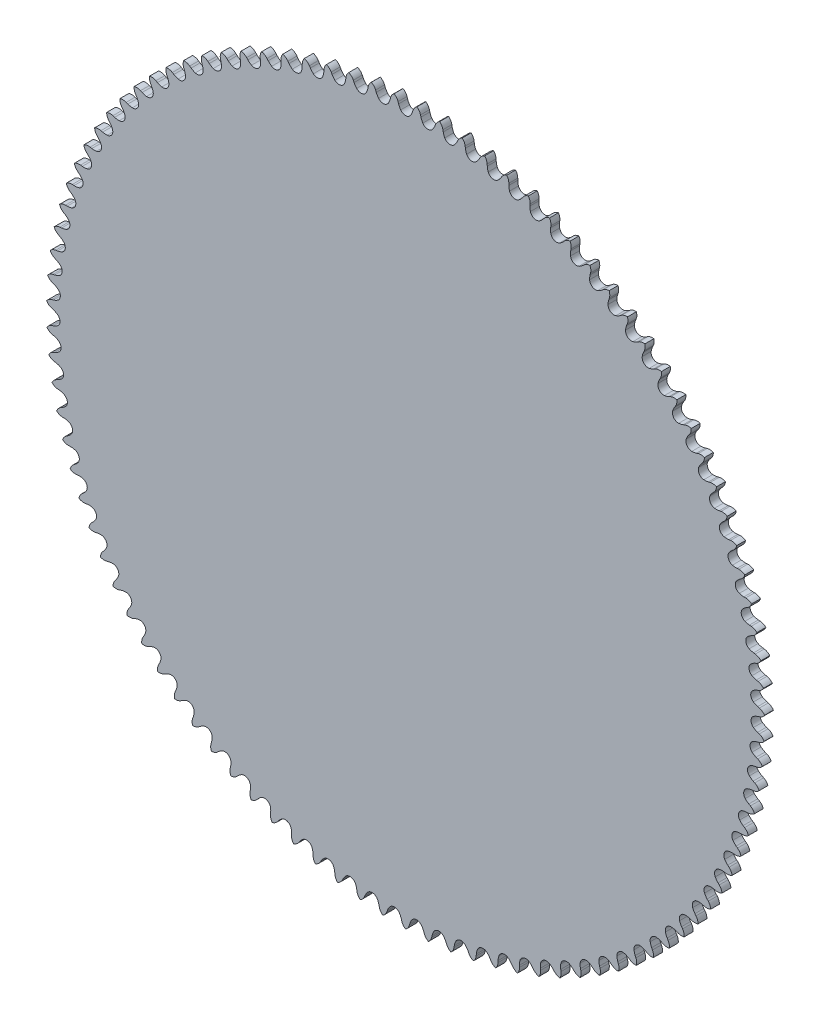
SolidWorks part; units mm, degrees
ref_plane "Front Plane" through (0, 0, 0) normal (0, 0, 1) x (1, 0, 0)
ref_plane "Top Plane" through (0, 0, 0) normal (0, 1, 0) x (1, 0, 0)
ref_plane "Right Plane" through (0, 0, 0) normal (1, 0, 0) x (0, 0, -1)
sketch "Sketch1" plane through (0, 0, 0) normal (0, 0, 1) x (1, 0, 0)
  line L0 (0, 0) -> (0, 31.4022) construction
  line L1 (-8.3395, 100.0695) -> (19.3734, 100.0695) construction
  line L2 (2.1477, 0) -> (2.1477, 31.4022) construction
  line L3 (-8.3395, 101.6075) -> (19.3734, 101.6075) construction
  line L4 (2.1477, 101.6075) -> (-1.38, 99.0813) construction
  line L5 (2.1477, 101.6075) -> (-1.9748, 100.2543) construction
  line L6 (-4.6205, 0) -> (-4.6205, 31.4022) construction
  line L7 (-8.3395, 99.9229) -> (19.3734, 99.9229) construction
  line L8 (-1.9748, 100.2543) -> (-2.1339, 100.7391)
  line L9 (0, 0) -> (-3.2426, 102.1478) construction
  line L10 (1.9748, 100.2543) -> (2.1339, 100.7391)
  line L11 (4.3877, 100.1777) -> (4.2596, 100.6716)
  line L12 (8.3294, 99.9272) -> (8.5189, 100.4009)
  line L13 (10.7325, 99.6978) -> (10.636, 100.1987)
  line L14 (14.6504, 99.1978) -> (14.8696, 99.6584)
  line L15 (17.0341, 98.8164) -> (16.9696, 99.3224)
  line L16 (20.9124, 98.0689) -> (21.1604, 98.5147)
  line L17 (23.2671, 97.537) -> (23.2349, 98.0462)
  line L18 (27.0902, 96.5451) -> (27.3659, 96.9743)
  line L19 (29.4065, 95.865) -> (29.4066, 96.3751)
  line L20 (33.1589, 94.6325) -> (33.4613, 95.0434)
  line L21 (35.4274, 93.8069) -> (35.4599, 94.316)
  line L22 (39.0941, 92.3389) -> (39.422, 92.7298)
  line L23 (41.3057, 91.3711) -> (41.3703, 91.8771)
  line L24 (44.8719, 89.6735) -> (45.2239, 90.0428)
  line L25 (47.0176, 88.5673) -> (47.1143, 89.0683)
  line L26 (50.469, 86.647) -> (50.8437, 86.9932)
  line L27 (52.5403, 85.407) -> (52.6685, 85.9008)
  line L28 (55.8629, 83.2716) -> (56.2588, 83.5934)
  line L29 (57.8513, 81.9027) -> (58.0106, 82.3874)
  line L30 (61.0319, 79.5609) -> (61.4474, 79.8569)
  line L31 (62.9294, 78.0687) -> (63.1191, 78.5423)
  line L32 (65.9551, 75.5299) -> (66.3885, 75.7989)
  line L33 (67.7542, 73.9203) -> (67.9735, 74.3809)
  line L34 (70.6127, 71.1947) -> (71.0623, 71.4357)
  line L35 (72.3061, 69.4742) -> (72.5542, 69.92)
  line L36 (74.9859, 66.5728) -> (75.45, 66.7848)
  line L37 (76.5668, 64.7484) -> (76.8427, 65.1775)
  line L38 (79.0573, 61.6829) -> (79.5338, 61.865)
  line L39 (80.5193, 59.7619) -> (80.8218, 60.1726)
  line L40 (82.8103, 56.5446) -> (83.2974, 56.6961)
  line L41 (84.1475, 54.5347) -> (84.4755, 54.9254)
  line L42 (86.2298, 51.1786) -> (86.7256, 51.2989)
  line L43 (87.4369, 49.0879) -> (87.789, 49.4571)
  line L44 (89.3022, 45.6065) -> (89.8046, 45.6952)
  line L45 (90.3742, 43.4435) -> (90.749, 43.7896)
  line L46 (92.0149, 39.8508) -> (92.5219, 39.9074)
  line L47 (92.9476, 37.6242) -> (93.3436, 37.9458)
  line L48 (94.3572, 33.9346) -> (94.8667, 33.959)
  line L49 (95.1467, 31.6533) -> (95.5623, 31.9492)
  line L50 (96.3195, 27.8818) -> (96.8296, 27.8738)
  line L51 (96.9627, 25.555) -> (97.3963, 25.8239)
  line L52 (97.8939, 21.7167) -> (98.4025, 21.6764)
  line L53 (98.3883, 19.3538) -> (98.838, 19.5947)
  line L54 (99.0742, 15.4642) -> (99.5792, 15.3916)
  line L55 (99.4177, 13.0747) -> (99.8818, 13.2865)
  line L56 (99.8555, 9.1493) -> (100.3549, 9.045)
  line L57 (100.0468, 6.7429) -> (100.5234, 6.9249)
  line L58 (100.2348, 2.7977) -> (100.7265, 2.6618)
  line L59 (100.2731, 0.3839) -> (100.7602, 0.5353)
  line L60 (100.2104, -3.5652) -> (100.6925, -3.732)
  line L61 (100.0955, -5.9765) -> (100.5913, -5.8563)
  line L62 (99.7825, -9.9138) -> (100.2531, -10.1108)
  line L63 (99.5149, -12.313) -> (100.0174, -12.2245)
  line L64 (98.9528, -16.2224) -> (99.41, -16.4489)
  line L65 (98.5337, -18.5998) -> (99.0407, -18.5433)
  line L66 (97.7247, -22.4657) -> (98.1666, -22.7207)
  line L67 (97.1556, -24.8117) -> (97.6652, -24.7875)
  line L68 (96.1031, -28.6186) -> (96.5279, -28.9011)
  line L69 (95.3863, -30.9238) -> (95.8964, -30.932)
  line L70 (94.0945, -34.6562) -> (94.5005, -34.9651)
  line L71 (93.233, -36.9113) -> (93.7415, -36.9518)
  line L72 (91.7071, -40.5543) -> (92.0927, -40.8883)
  line L73 (90.7042, -42.7502) -> (91.2092, -42.8229)
  line L74 (88.9503, -46.289) -> (89.314, -46.6468)
  line L75 (87.8102, -48.4169) -> (88.3095, -48.5215)
  line L76 (85.8354, -51.8374) -> (86.1756, -52.2176)
  line L77 (84.5626, -53.8887) -> (85.0543, -54.0247)
  line L78 (82.3748, -57.1771) -> (82.6903, -57.578)
  line L79 (80.9746, -59.1435) -> (81.4566, -59.3104)
  line L80 (78.5826, -62.2865) -> (78.872, -62.7066)
  line L81 (77.0604, -64.1602) -> (77.5309, -64.3573)
  line L82 (74.4739, -67.1451) -> (74.7361, -67.5828)
  line L83 (72.836, -68.9185) -> (73.293, -69.1451)
  line L84 (70.0654, -71.7334) -> (70.2992, -72.1868)
  line L85 (68.3183, -73.3992) -> (68.76, -73.6544)
  line L86 (65.3747, -76.0328) -> (65.5793, -76.5001)
  line L87 (63.5254, -77.5845) -> (63.9501, -77.8671)
  line L88 (60.4208, -80.026) -> (60.5954, -80.5054)
  line L89 (58.4768, -81.4573) -> (58.8827, -81.7663)
  line L90 (55.2236, -83.697) -> (55.3674, -84.1865)
  line L91 (53.1928, -85.0021) -> (53.5782, -85.3363)
  line L92 (49.804, -87.031) -> (49.9165, -87.5286)
  line L93 (47.6945, -88.2047) -> (48.058, -88.5626)
  line L94 (44.1839, -90.0145) -> (44.2646, -90.5183)
  line L95 (42.0042, -91.0521) -> (42.3443, -91.4323)
  line L96 (38.3859, -92.6356) -> (38.4345, -93.1435)
  line L97 (36.1447, -93.5328) -> (36.46, -93.9339)
  line L98 (32.4333, -94.8837) -> (32.4495, -95.3936)
  line L99 (30.1397, -95.637) -> (30.429, -96.0572)
  line L100 (26.3501, -96.7497) -> (26.334, -97.2596)
  line L101 (24.0134, -97.356) -> (24.2754, -97.7937)
  line L102 (20.1608, -98.2261) -> (20.1124, -98.734)
  line L103 (17.7903, -98.683) -> (18.024, -99.1365)
  line L104 (13.8903, -99.3071) -> (13.8098, -99.8108)
  line L105 (11.4957, -99.6127) -> (11.7001, -100.0801)
  line L106 (7.5639, -99.9881) -> (7.4516, -100.4857)
  line L107 (5.1547, -100.1412) -> (5.3291, -100.6206)
  line L108 (1.207, -100.2665) -> (1.0634, -100.756)
  line L109 (-1.207, -100.2665) -> (-1.0634, -100.756)
  line L110 (-5.1547, -100.1412) -> (-5.3291, -100.6206)
  line L111 (-7.5639, -99.9881) -> (-7.4516, -100.4857)
  line L112 (-11.4957, -99.6127) -> (-11.7001, -100.0801)
  line L113 (-13.8903, -99.3071) -> (-13.8098, -99.8108)
  line L114 (-17.7903, -98.683) -> (-18.024, -99.1365)
  line L115 (-20.1608, -98.2261) -> (-20.1124, -98.734)
  line L116 (-24.0134, -97.356) -> (-24.2754, -97.7937)
  line L117 (-26.3501, -96.7497) -> (-26.334, -97.2596)
  line L118 (-30.1397, -95.637) -> (-30.429, -96.0572)
  line L119 (-32.4333, -94.8837) -> (-32.4495, -95.3936)
  line L120 (-36.1447, -93.5328) -> (-36.46, -93.9339)
  line L121 (-38.3859, -92.6356) -> (-38.4345, -93.1435)
  line L122 (-42.0042, -91.0521) -> (-42.3443, -91.4323)
  line L123 (-44.1839, -90.0145) -> (-44.2646, -90.5183)
  line L124 (-47.6945, -88.2047) -> (-48.058, -88.5626)
  line L125 (-49.804, -87.031) -> (-49.9165, -87.5286)
  line L126 (-53.1928, -85.0021) -> (-53.5782, -85.3363)
  line L127 (-55.2236, -83.697) -> (-55.3674, -84.1865)
  line L128 (-58.4768, -81.4573) -> (-58.8827, -81.7663)
  line L129 (-60.4208, -80.026) -> (-60.5954, -80.5054)
  line L130 (-63.5254, -77.5845) -> (-63.9501, -77.8671)
  line L131 (-65.3747, -76.0328) -> (-65.5793, -76.5001)
  line L132 (-68.3183, -73.3992) -> (-68.76, -73.6544)
  line L133 (-70.0654, -71.7334) -> (-70.2992, -72.1868)
  line L134 (-72.836, -68.9185) -> (-73.293, -69.1451)
  line L135 (-74.4739, -67.1451) -> (-74.7361, -67.5828)
  line L136 (-77.0604, -64.1602) -> (-77.5309, -64.3573)
  line L137 (-78.5826, -62.2865) -> (-78.872, -62.7066)
  line L138 (-80.9746, -59.1435) -> (-81.4566, -59.3104)
  line L139 (-82.3748, -57.1771) -> (-82.6903, -57.578)
  line L140 (-84.5626, -53.8887) -> (-85.0543, -54.0247)
  line L141 (-85.8354, -51.8374) -> (-86.1756, -52.2176)
  line L142 (-87.8102, -48.4169) -> (-88.3095, -48.5215)
  line L143 (-88.9503, -46.289) -> (-89.314, -46.6468)
  line L144 (-90.7042, -42.7502) -> (-91.2092, -42.8229)
  line L145 (-91.7071, -40.5543) -> (-92.0927, -40.8883)
  line L146 (-93.233, -36.9113) -> (-93.7415, -36.9518)
  line L147 (-94.0945, -34.6562) -> (-94.5005, -34.9651)
  line L148 (-95.3863, -30.9238) -> (-95.8964, -30.932)
  line L149 (-96.1031, -28.6186) -> (-96.5279, -28.9011)
  line L150 (-97.1556, -24.8117) -> (-97.6652, -24.7875)
  line L151 (-97.7247, -22.4657) -> (-98.1666, -22.7207)
  line L152 (-98.5337, -18.5998) -> (-99.0407, -18.5433)
  line L153 (-98.9528, -16.2224) -> (-99.41, -16.4489)
  line L154 (-99.5149, -12.313) -> (-100.0174, -12.2245)
  line L155 (-99.7825, -9.9138) -> (-100.2531, -10.1108)
  line L156 (-100.0955, -5.9765) -> (-100.5913, -5.8563)
  line L157 (-100.2104, -3.5652) -> (-100.6925, -3.732)
  line L158 (-100.2731, 0.3839) -> (-100.7602, 0.5353)
  line L159 (-100.2348, 2.7977) -> (-100.7265, 2.6618)
  line L160 (-100.0468, 6.7429) -> (-100.5234, 6.9249)
  line L161 (-99.8555, 9.1493) -> (-100.3549, 9.045)
  line L162 (-99.4177, 13.0747) -> (-99.8818, 13.2865)
  line L163 (-99.0742, 15.4642) -> (-99.5792, 15.3916)
  line L164 (-98.3883, 19.3538) -> (-98.838, 19.5947)
  line L165 (-97.8939, 21.7167) -> (-98.4025, 21.6764)
  line L166 (-96.9627, 25.555) -> (-97.3963, 25.8239)
  line L167 (-96.3195, 27.8818) -> (-96.8296, 27.8738)
  line L168 (-95.1467, 31.6533) -> (-95.5623, 31.9492)
  line L169 (-94.3572, 33.9346) -> (-94.8667, 33.959)
  line L170 (-92.9476, 37.6242) -> (-93.3436, 37.9458)
  line L171 (-92.0149, 39.8508) -> (-92.5219, 39.9074)
  line L172 (-90.3742, 43.4435) -> (-90.749, 43.7896)
  line L173 (-89.3022, 45.6065) -> (-89.8046, 45.6952)
  line L174 (-87.4369, 49.0879) -> (-87.789, 49.4571)
  line L175 (-86.2298, 51.1786) -> (-86.7256, 51.2989)
  line L176 (-84.1475, 54.5347) -> (-84.4755, 54.9254)
  line L177 (-82.8103, 56.5446) -> (-83.2974, 56.6961)
  line L178 (-80.5193, 59.7619) -> (-80.8218, 60.1726)
  line L179 (-79.0573, 61.6829) -> (-79.5338, 61.865)
  line L180 (-76.5668, 64.7484) -> (-76.8427, 65.1775)
  line L181 (-74.9859, 66.5728) -> (-75.45, 66.7848)
  line L182 (-72.3061, 69.4742) -> (-72.5542, 69.92)
  line L183 (-70.6127, 71.1947) -> (-71.0623, 71.4357)
  line L184 (-67.7542, 73.9203) -> (-67.9735, 74.3809)
  line L185 (-65.9551, 75.5299) -> (-66.3885, 75.7989)
  line L186 (-62.9294, 78.0687) -> (-63.1191, 78.5423)
  line L187 (-61.0319, 79.5609) -> (-61.4474, 79.8569)
  line L188 (-57.8513, 81.9027) -> (-58.0106, 82.3874)
  line L189 (-55.8629, 83.2716) -> (-56.2588, 83.5934)
  line L190 (-52.5403, 85.407) -> (-52.6685, 85.9008)
  line L191 (-50.469, 86.647) -> (-50.8437, 86.9932)
  line L192 (-47.0176, 88.5673) -> (-47.1143, 89.0683)
  line L193 (-44.8719, 89.6735) -> (-45.2239, 90.0428)
  line L194 (-41.3057, 91.3711) -> (-41.3703, 91.8771)
  line L195 (-39.0941, 92.3389) -> (-39.422, 92.7298)
  line L196 (-35.4274, 93.8069) -> (-35.4599, 94.316)
  line L197 (-33.1589, 94.6325) -> (-33.4613, 95.0434)
  line L198 (-29.4065, 95.865) -> (-29.4066, 96.3751)
  line L199 (-27.0902, 96.5451) -> (-27.3659, 96.9743)
  line L200 (-23.2671, 97.537) -> (-23.2349, 98.0462)
  line L201 (-20.9124, 98.0689) -> (-21.1604, 98.5147)
  line L202 (-17.0341, 98.8164) -> (-16.9696, 99.3224)
  line L203 (-14.6504, 99.1978) -> (-14.8696, 99.6584)
  line L204 (-10.7325, 99.6978) -> (-10.636, 100.1987)
  line L205 (-8.3294, 99.9272) -> (-8.5189, 100.4009)
  line L206 (-4.3877, 100.1777) -> (-4.2596, 100.6716)
  circle A0 centre (0, 0) radius 100.0695 construction
  arc A2 (-1.9748, 100.2543) -> (-1.38, 99.0813) centre (2.1477, 101.6075) ccw
  arc A4 (-2.1339, 100.7391) -> (-3.2426, 102.1478) centre (-4.6205, 99.9229) ccw
  arc A5 (-1.38, 99.0813) -> (1.38, 99.0813) centre (0, 100.0695) ccw
  arc A6 (1.9748, 100.2543) -> (1.38, 99.0813) centre (-2.1477, 101.6075) cw
  arc A7 (2.1339, 100.7391) -> (3.2426, 102.1478) centre (4.6205, 99.9229) cw
  arc A8 (4.2596, 100.6716) -> (3.2426, 102.1478) centre (1.7263, 100.0147) ccw
  arc A9 (4.3877, 100.1777) -> (4.9069, 98.9694) centre (8.5877, 101.2667) ccw
  arc A10 (4.9069, 98.9694) -> (7.6614, 98.7943) centre (6.3468, 99.8681) ccw
  arc A11 (8.3294, 99.9272) -> (7.6614, 98.7943) centre (4.3009, 101.5392) cw
  arc A12 (8.5189, 100.4009) -> (9.7147, 101.7365) centre (10.9487, 99.4287) cw
  arc A13 (10.636, 100.1987) -> (9.7147, 101.7365) centre (8.0662, 99.7039) ccw
  arc A14 (10.7325, 99.6978) -> (11.174, 98.4589) centre (14.9932, 100.5182) ccw
  arc A15 (11.174, 98.4589) -> (13.9119, 98.1095) centre (12.668, 99.2645) ccw
  arc A16 (14.6504, 99.1978) -> (13.9119, 98.1095) centre (10.7323, 101.0619) cw
  arc A17 (14.8696, 99.6584) -> (16.1476, 100.9155) centre (17.2328, 98.5341) cw
  arc A18 (16.9696, 99.3224) -> (16.1476, 100.9155) centre (14.3736, 98.9916) ccw
  arc A19 (17.0341, 98.8164) -> (17.3962, 97.552) centre (21.3383, 99.3649) ccw
  arc A20 (17.3962, 97.552) -> (20.1063, 97.0296) centre (18.9383, 98.2612) ccw
  arc A21 (20.9124, 98.0689) -> (20.1063, 97.0296) centre (17.1204, 100.1778) cw
  arc A22 (21.1604, 98.5147) -> (22.5156, 99.6882) centre (23.4475, 97.2427) cw
  arc A23 (23.2349, 98.0462) -> (22.5156, 99.6882) centre (20.623, 97.8806) ccw
  arc A24 (23.2671, 97.537) -> (23.5483, 96.2522) centre (27.5974, 97.8115) ccw
  arc A25 (23.5483, 96.2522) -> (26.2199, 95.5591) centre (25.1323, 96.8622) ccw
  arc A26 (27.0902, 96.5451) -> (26.2199, 95.5591) centre (23.4396, 98.8903) cw
  arc A27 (27.3659, 96.9743) -> (28.7929, 98.0595) centre (29.5678, 95.5598) cw
  arc A28 (29.4066, 96.3751) -> (28.7929, 98.0595) centre (26.7895, 96.3756) ccw
  arc A29 (29.4065, 95.865) -> (29.6056, 94.5649) centre (33.7454, 95.8642) ccw
  arc A30 (29.6056, 94.5649) -> (32.2278, 93.7037) centre (31.225, 95.0732) ccw
  arc A31 (33.1589, 94.6325) -> (32.2278, 93.7037) centre (29.6645, 97.2045) cw
  arc A32 (33.4613, 95.0434) -> (34.9542, 96.0359) centre (35.5691, 93.4921) cw
  arc A33 (35.4599, 94.316) -> (34.9542, 96.0359) centre (32.8481, 94.4825) ccw
  arc A34 (35.4274, 93.8069) -> (35.5436, 92.4968) centre (39.7576, 93.5309) ccw
  arc A35 (35.5436, 92.4968) -> (38.106, 91.471) centre (37.1921, 92.9014) ccw
  arc A36 (39.0941, 92.3389) -> (38.106, 91.471) centre (35.7698, 95.1274) cw
  arc A37 (39.422, 92.7298) -> (40.9748, 93.6256) centre (41.4271, 91.0479) cw
  arc A38 (41.3703, 91.8771) -> (40.9748, 93.6256) centre (38.7744, 92.2089) ccw
  arc A39 (41.3057, 91.3711) -> (41.3386, 90.0563) centre (45.6096, 90.821) ccw
  arc A40 (41.3386, 90.0563) -> (43.8307, 88.87) centre (43.0094, 90.3555) ccw
  arc A41 (44.8719, 89.6735) -> (43.8307, 88.87) centre (41.7312, 92.6672) cw
  arc A42 (45.2239, 90.0428) -> (46.8304, 90.8383) centre (47.1183, 88.2372) cw
  arc A43 (47.1143, 89.0683) -> (46.8304, 90.8383) centre (44.5446, 89.564) ccw
  arc A44 (47.0176, 88.5673) -> (46.9671, 87.2531) centre (51.278, 87.7454) ccw
  arc A45 (46.9671, 87.2531) -> (49.3789, 85.9112) centre (48.6535, 87.4457) ccw
  arc A46 (50.469, 86.647) -> (49.3789, 85.9112) centre (47.5245, 89.8339) cw
  arc A47 (50.8437, 86.9932) -> (52.4975, 87.6853) centre (52.6198, 85.0711) cw
  arc A48 (52.6685, 85.9008) -> (52.4975, 87.6853) centre (50.1354, 86.5585) ccw
  arc A49 (52.5403, 85.407) -> (52.4065, 84.0986) centre (56.7399, 84.3165) ccw
  arc A50 (52.4065, 84.0986) -> (54.7284, 82.6064) centre (54.1017, 84.1839) ccw
  arc A51 (55.8629, 83.2716) -> (54.7284, 82.6064) centre (53.1264, 86.6388) cw
  arc A52 (56.2588, 83.5934) -> (57.9531, 84.1792) centre (57.9094, 81.5625) cw
  arc A53 (58.0106, 82.3874) -> (57.9531, 84.1792) centre (55.5243, 83.2044) ccw
  arc A54 (57.8513, 81.9027) -> (57.6348, 80.6055) centre (61.9734, 80.5481) ccw
  arc A55 (57.6348, 80.6055) -> (59.8574, 78.969) centre (59.332, 80.583) ccw
  arc A56 (61.0319, 79.5609) -> (59.8574, 78.969) centre (58.5144, 83.0949) cw
  arc A57 (61.4474, 79.8569) -> (63.1754, 80.3341) centre (62.9658, 77.7254) cw
  arc A58 (63.1191, 78.5423) -> (63.1754, 80.3341) centre (60.6897, 79.5153) ccw
  arc A59 (62.9294, 78.0687) -> (62.6311, 76.7878) centre (66.9573, 76.4553) ccw
  arc A60 (62.6311, 76.7878) -> (64.7454, 75.0136) centre (64.3235, 76.6577) ccw
  arc A61 (65.9551, 75.5299) -> (64.7454, 75.0136) centre (63.6668, 79.2164) cw
  arc A62 (66.3885, 75.7989) -> (68.1433, 76.1655) centre (67.7687, 73.5754) cw
  arc A63 (67.9735, 74.3809) -> (68.1433, 76.1655) centre (65.6107, 75.5061) ccw
  arc A64 (67.7542, 73.9203) -> (67.3752, 72.6609) centre (71.6716, 72.0547) ccw
  arc A65 (67.3752, 72.6609) -> (69.3727, 70.7562) centre (69.0559, 72.4237) ccw
  arc A66 (70.6127, 71.1947) -> (69.3727, 70.7562) centre (68.5628, 75.0189) cw
  arc A67 (71.0623, 71.4357) -> (72.8368, 71.6902) centre (72.2987, 69.1291) cw
  arc A68 (72.5542, 69.92) -> (72.8368, 71.6902) centre (70.2675, 71.1928) ccw
  arc A69 (72.3061, 69.4742) -> (71.848, 68.2414) centre (76.0973, 67.364) ccw
  arc A70 (71.848, 68.2414) -> (73.7207, 66.2139) centre (73.5103, 67.8981) ccw
  arc A71 (74.9859, 66.5728) -> (73.7207, 66.2139) centre (73.1828, 70.5194) cw
  arc A72 (75.45, 66.7848) -> (77.2371, 66.9263) centre (76.5376, 64.4045) cw
  arc A73 (76.8427, 65.1775) -> (77.2371, 66.9263) centre (74.6413, 66.5928) ccw
  arc A74 (76.5668, 64.7484) -> (76.0315, 63.5471) centre (80.2166, 62.4019) ccw
  arc A75 (76.0315, 63.5471) -> (77.7718, 61.4049) centre (77.6686, 63.0991) ccw
  arc A76 (79.0573, 61.6829) -> (77.7718, 61.4049) centre (77.5081, 65.7358) cw
  arc A77 (79.5338, 61.865) -> (81.3263, 61.8929) centre (80.4682, 59.4205) cw
  arc A78 (80.8218, 60.1726) -> (81.3263, 61.8929) centre (78.7146, 61.7247) ccw
  arc A79 (80.5193, 59.7619) -> (79.9088, 58.5969) centre (84.0128, 57.1887) ccw
  arc A80 (79.9088, 58.5969) -> (81.5098, 56.3487) centre (81.5142, 58.046) ccw
  arc A81 (82.8103, 56.5446) -> (81.5098, 56.3487) centre (81.5212, 60.6876) cw
  arc A82 (83.2974, 56.6961) -> (85.088, 56.6102) centre (84.0749, 54.1972) cw
  arc A83 (84.4755, 54.9254) -> (85.088, 56.6102) centre (82.471, 56.608) ccw
  arc A84 (84.1475, 54.5347) -> (83.4643, 53.4108) centre (87.4708, 51.7451) ccw
  arc A85 (83.4643, 53.4108) -> (84.9195, 51.0656) centre (85.0316, 52.7592) ccw
  arc A86 (86.2298, 51.1786) -> (84.9195, 51.0656) centre (85.2062, 55.395) cw
  arc A87 (86.7256, 51.2989) -> (88.5072, 51.0996) centre (87.343, 48.7558) cw
  arc A88 (87.789, 49.4571) -> (88.5072, 51.0996) centre (85.8952, 51.2634) ccw
  arc A89 (87.4369, 49.0879) -> (86.6838, 48.0097) centre (90.5766, 46.0932) ccw
  arc A90 (86.6838, 48.0097) -> (87.9873, 45.5768) centre (88.2066, 47.26) ccw
  arc A91 (89.3022, 45.6065) -> (87.9873, 45.5768) centre (88.548, 49.8794) cw
  arc A92 (89.8046, 45.6952) -> (91.5699, 45.3833) centre (90.2595, 43.118) cw
  arc A93 (90.749, 43.7896) -> (91.5699, 45.3833) centre (88.9736, 45.7124) ccw
  arc A94 (90.3742, 43.4435) -> (89.5543, 42.4152) centre (93.3176, 40.2556) ccw
  arc A95 (89.5543, 42.4152) -> (90.7008, 39.9046) centre (91.0265, 41.5704) ccw
  arc A96 (92.0149, 39.8508) -> (90.7008, 39.9046) centre (91.5332, 44.1629) cw
  arc A97 (92.5219, 39.9074) -> (94.2639, 39.4842) centre (92.8125, 37.3065) cw
  arc A98 (93.3436, 37.9458) -> (94.2639, 39.4842) centre (91.6938, 39.9773) ccw
  arc A99 (92.9476, 37.6242) -> (92.0641, 36.6499) centre (95.6829, 34.256) ccw
  arc A100 (92.0641, 36.6499) -> (93.0491, 34.0716) centre (93.4798, 35.7134) ccw
  arc A101 (94.3572, 33.9346) -> (93.0491, 34.0716) centre (94.1499, 38.2686) cw
  arc A102 (94.8667, 33.959) -> (96.5784, 33.4261) centre (94.9917, 31.3449) cw
  arc A103 (95.5623, 31.9492) -> (96.5784, 33.4261) centre (94.0447, 34.0812) ccw
  arc A104 (95.1467, 31.6533) -> (94.2032, 30.737) centre (97.6629, 28.1185) ccw
  arc A105 (94.2032, 30.737) -> (95.0227, 28.1015) centre (95.5566, 29.7127) ccw
  arc A106 (96.3195, 27.8818) -> (95.0227, 28.1015) centre (96.3875, 32.2202) cw
  arc A107 (96.8296, 27.8738) -> (98.504, 27.2334) centre (96.7885, 25.257) cw
  arc A108 (97.3963, 25.8239) -> (98.504, 27.2334) centre (96.0169, 28.0479) ccw
  arc A109 (96.9627, 25.555) -> (95.963, 24.7004) centre (99.2497, 21.8677) ccw
  arc A110 (95.963, 24.7004) -> (96.6137, 22.0182) centre (97.2487, 23.5923) ccw
  arc A111 (97.8939, 21.7167) -> (96.6137, 22.0182) centre (98.237, 26.0421) cw
  arc A112 (98.4025, 21.6764) -> (100.0329, 20.9311) centre (98.1955, 19.0675) cw
  arc A113 (98.838, 19.5947) -> (100.0329, 20.9311) centre (97.6025, 21.9017) ccw
  arc A114 (98.3883, 19.3538) -> (97.3364, 18.5643) centre (100.4368, 15.5289) ccw
  arc A115 (97.3364, 18.5643) -> (97.8157, 15.8462) centre (98.5493, 17.3769) ccw
  arc A116 (99.0742, 15.4642) -> (97.8157, 15.8462) centre (99.6909, 19.7591) cw
  arc A117 (99.5792, 15.3916) -> (101.159, 14.5445) centre (99.2072, 12.8011) cw
  arc A118 (99.8818, 13.2865) -> (101.159, 14.5445) centre (98.7951, 15.6673) ccw
  arc A119 (99.4177, 13.0747) -> (98.3179, 12.3535) centre (101.2195, 9.1275) ccw
  arc A120 (98.3179, 12.3535) -> (98.6238, 9.6105) centre (99.453, 11.0915) ccw
  arc A121 (99.8555, 9.1493) -> (98.6238, 9.6105) centre (100.7434, 13.3965) cw
  arc A122 (100.3549, 9.045) -> (101.8778, 8.0993) centre (99.8193, 6.4833) cw
  arc A123 (100.5234, 6.9249) -> (101.8778, 8.0993) centre (99.5898, 9.3698) ccw
  arc A124 (100.0468, 6.7429) -> (98.9034, 6.0929) centre (101.5946, 2.6894) ccw
  arc A125 (98.9034, 6.0929) -> (99.0348, 3.336) centre (99.9562, 4.7615) ccw
  arc A126 (100.2348, 2.7977) -> (99.0348, 3.336) centre (101.3902, 6.98) cw
  arc A127 (100.7265, 2.6618) -> (102.1864, 1.6215) centre (100.0295, 0.1393) cw
  arc A128 (100.7602, 0.5353) -> (102.1864, 1.6215) centre (99.9836, 3.0345) ccw
  arc A129 (100.2731, 0.3839) -> (99.0908, -0.1922) centre (101.5606, -3.7596) ccw
  arc A130 (99.0908, -0.1922) -> (99.047, -2.9519) centre (100.057, -1.5877) ccw
  arc A131 (100.2104, -3.5652) -> (99.047, -2.9519) centre (101.6288, 0.5354) cw
  arc A132 (100.6925, -3.732) -> (102.0835, -4.8628) centre (99.837, -6.2053) cw
  arc A133 (100.5913, -5.8563) -> (102.0835, -4.8628) centre (99.9748, -3.3129) ccw
  arc A134 (100.0955, -5.9765) -> (98.8791, -6.4765) centre (101.1177, -10.1934) ccw
  arc A135 (98.8791, -6.4765) -> (98.6603, -9.2279) centre (99.7548, -7.9305) ccw
  arc A136 (99.7825, -9.9138) -> (98.6603, -9.2279) centre (101.4581, -5.9114) cw
  arc A137 (100.2531, -10.1108) -> (101.5696, -11.3276) centre (99.2424, -12.5248) cw
  arc A138 (100.0174, -12.2245) -> (101.5696, -11.3276) centre (99.5634, -9.6471) ccw
  arc A139 (99.5149, -12.313) -> (98.2692, -12.7348) centre (100.2676, -16.5861) ccw
  arc A140 (98.2692, -12.7348) -> (97.8764, -15.4667) centre (99.051, -14.2414) ccw
  arc A141 (98.9528, -16.2224) -> (97.8764, -15.4667) centre (100.8789, -12.3344) cw
  arc A142 (99.41, -16.4489) -> (100.6466, -17.7467) centre (98.2482, -18.794) cw
  arc A143 (99.0407, -18.5433) -> (100.6466, -17.7467) centre (98.7511, -15.9423) ccw
  arc A144 (98.5337, -18.5998) -> (97.2637, -18.9418) centre (99.0138, -22.9121) ccw
  arc A145 (97.2637, -18.9418) -> (96.6984, -21.6433) centre (97.9483, -20.4949) ccw
  arc A146 (97.7247, -22.4657) -> (96.6984, -21.6433) centre (99.8935, -18.7077) cw
  arc A147 (98.1666, -22.7207) -> (99.3184, -24.0944) centre (96.8585, -24.9874) cw
  arc A148 (97.6652, -24.7875) -> (99.3184, -24.0944) centre (97.5411, -22.1734) ccw
  arc A149 (97.1556, -24.8117) -> (95.8665, -25.0725) centre (97.3613, -29.1458) ccw
  arc A150 (95.8665, -25.0725) -> (95.131, -27.7327) centre (96.4513, -26.6659) ccw
  arc A151 (96.1031, -28.6186) -> (95.131, -27.7327) centre (98.5059, -25.0057) cw
  arc A152 (96.5279, -28.9011) -> (97.5903, -30.3451) centre (95.0786, -31.0802) cw
  arc A153 (95.8964, -30.932) -> (97.5903, -30.3451) centre (95.9384, -28.3152) ccw
  arc A154 (95.3863, -30.9238) -> (94.0833, -31.1022) centre (95.3167, -35.2622) ccw
  arc A155 (94.0833, -31.1022) -> (93.1806, -33.7104) centre (94.5658, -32.7295) ccw
  arc A156 (94.0945, -34.6562) -> (93.1806, -33.7104) centre (96.7216, -31.203) cw
  arc A157 (94.5005, -34.9651) -> (95.4692, -36.4735) centre (92.916, -37.0479) cw
  arc A158 (93.7415, -36.9518) -> (95.4692, -36.4735) centre (93.9494, -34.343) ccw
  arc A159 (93.233, -36.9113) -> (91.9213, -37.0067) centre (92.8884, -41.2365) ccw
  arc A160 (91.9213, -37.0067) -> (90.8549, -39.5525) centre (92.2996, -38.6614) ccw
  arc A161 (91.7071, -40.5543) -> (90.8549, -39.5525) centre (94.5479, -37.2746) cw
  arc A162 (92.0927, -40.8883) -> (92.9637, -42.4551) centre (90.3792, -42.8664) cw
  arc A163 (91.2092, -42.8229) -> (92.9637, -42.4551) centre (91.5821, -40.2325) ccw
  arc A164 (90.7042, -42.7502) -> (89.3891, -42.7622) centre (90.086, -47.0449) ccw
  arc A165 (89.3891, -42.7622) -> (88.1634, -45.2352) centre (89.6617, -44.4375) ccw
  arc A166 (88.9503, -46.289) -> (88.1634, -45.2352) centre (91.9934, -43.1962) cw
  arc A167 (89.314, -46.6468) -> (90.0839, -48.2658) centre (87.4785, -48.5123) cw
  arc A168 (88.3095, -48.5215) -> (90.0839, -48.2658) centre (88.846, -45.96) ccw
  arc A169 (87.8102, -48.4169) -> (86.497, -48.3455) centre (86.9208, -52.6637) ccw
  arc A170 (86.497, -48.3455) -> (85.1169, -50.7358) centre (86.6628, -50.0348) ccw
  arc A171 (85.8354, -51.8374) -> (85.1169, -50.7358) centre (89.0685, -48.9438) cw
  arc A172 (86.1756, -52.2176) -> (86.8413, -53.8821) centre (84.2255, -53.9629) cw
  arc A173 (85.0543, -54.0247) -> (86.8413, -53.8821) centre (85.7521, -51.5024) ccw
  arc A174 (84.5626, -53.8887) -> (83.2566, -53.7342) centre (83.4057, -58.0706) ccw
  arc A175 (83.2566, -53.7342) -> (81.7277, -56.0321) centre (83.3149, -55.4305) ccw
  arc A176 (82.3748, -57.1771) -> (81.7277, -56.0321) centre (85.785, -54.4943) cw
  arc A177 (82.6903, -57.578) -> (83.2491, -59.2814) centre (80.6334, -59.1962) cw
  arc A178 (81.4566, -59.3104) -> (83.2491, -59.2814) centre (82.313, -56.8375) ccw
  arc A179 (80.9746, -59.1435) -> (79.6809, -58.9065) centre (79.5547, -63.2436) ccw
  arc A180 (79.6809, -58.9065) -> (78.0094, -61.1028) centre (79.6315, -60.6031) ccw
  arc A181 (78.5826, -62.2865) -> (78.0094, -61.1028) centre (82.1561, -59.8254) cw
  arc A182 (78.872, -62.7066) -> (79.3216, -64.442) centre (76.7166, -64.1911) cw
  arc A183 (77.5309, -64.3573) -> (79.3216, -64.442) centre (78.5424, -61.9436) ccw
  arc A184 (77.0604, -64.1602) -> (75.7844, -63.8415) centre (75.3834, -68.1619) ccw
  arc A185 (75.7844, -63.8415) -> (73.977, -65.9274) centre (75.6275, -65.5316) ccw
  arc A186 (74.4739, -67.1451) -> (73.977, -65.9274) centre (78.1963, -64.9156) cw
  arc A187 (74.7361, -67.5828) -> (75.0747, -69.3432) centre (72.4909, -68.9275) cw
  arc A188 (73.293, -69.1451) -> (75.0747, -69.3432) centre (74.4556, -66.8004) ccw
  arc A189 (72.836, -68.9185) -> (71.5827, -68.5195) centre (70.9085, -72.8058) ccw
  arc A190 (71.5827, -68.5195) -> (69.6466, -70.4866) centre (71.319, -70.1963) ccw
  arc A191 (70.0654, -71.7334) -> (69.6466, -70.4866) centre (73.9217, -69.7444) cw
  arc A192 (70.2992, -72.1868) -> (70.5256, -73.9651) centre (67.9733, -73.3864) cw
  arc A193 (68.76, -73.6544) -> (70.5256, -73.9651) centre (70.069, -71.3882) ccw
  arc A194 (68.3183, -73.3992) -> (67.0928, -72.9216) centre (66.1481, -77.1565) ccw
  arc A195 (67.0928, -72.9216) -> (65.0359, -74.7619) centre (66.7233, -74.5783) ccw
  arc A196 (65.3747, -76.0328) -> (65.0359, -74.7619) centre (69.3494, -74.2924) cw
  arc A197 (65.5793, -76.5001) -> (65.6924, -78.2892) centre (63.182, -77.5498) cw
  arc A198 (63.9501, -77.8671) -> (65.6924, -78.2892) centre (65.4002, -75.6885) ccw
  arc A199 (63.5254, -77.5845) -> (62.3328, -77.0301) centre (61.1214, -81.1965) ccw
  arc A200 (62.3328, -77.0301) -> (60.1633, -78.7363) centre (61.8589, -78.66) ccw
  arc A201 (60.4208, -80.026) -> (60.1633, -78.7363) centre (64.4978, -78.5413) cw
  arc A202 (60.5954, -80.5054) -> (60.5948, -82.298) centre (58.1363, -81.4009) cw
  arc A203 (58.8827, -81.7663) -> (60.5948, -82.298) centre (60.468, -79.684) ccw
  arc A204 (58.4768, -81.4573) -> (57.3217, -80.8284) centre (55.8485, -84.9096) ccw
  arc A205 (57.3217, -80.8284) -> (55.0484, -82.3935) centre (56.7454, -82.4249) ccw
  arc A206 (55.2236, -83.697) -> (55.0484, -82.3935) centre (59.3866, -82.4738) cw
  arc A207 (55.3674, -84.1865) -> (55.2531, -85.9755) centre (52.8565, -84.9242) cw
  arc A208 (53.5782, -85.3363) -> (55.2531, -85.9755) centre (55.2924, -83.3587) ccw
  arc A209 (53.1928, -85.0021) -> (52.0799, -84.3013) centre (50.3508, -88.2808) ccw
  arc A210 (52.0799, -84.3013) -> (49.7118, -85.719) centre (51.4035, -85.858) ccw
  arc A211 (49.804, -87.031) -> (49.7118, -85.719) centre (54.0362, -86.0743) cw
  arc A212 (49.9165, -87.5286) -> (49.689, -89.3068) centre (47.3638, -88.1056) cw
  arc A213 (48.058, -88.5626) -> (49.689, -89.3068) centre (49.8942, -86.6978) ccw
  arc A214 (47.6945, -88.2047) -> (46.6283, -87.4346) centre (44.6503, -91.2965) ccw
  arc A215 (46.6283, -87.4346) -> (44.1751, -88.6994) centre (45.8545, -88.9454) ccw
  arc A216 (44.1839, -90.0145) -> (44.1751, -88.6994) centre (48.4682, -89.3282) cw
  arc A217 (44.2646, -90.5183) -> (43.9247, -92.2784) centre (41.6805, -90.9322) cw
  arc A218 (42.3443, -91.4323) -> (43.9247, -92.2784) centre (44.295, -89.6877) ccw
  arc A219 (42.0042, -91.0521) -> (40.989, -90.216) centre (38.77, -93.9446) ccw
  arc A220 (40.989, -90.216) -> (38.4605, -91.3225) centre (40.1209, -91.6746) ccw
  arc A221 (38.3859, -92.6356) -> (38.4605, -91.3225) centre (42.7051, -92.2224) cw
  arc A222 (38.4345, -93.1435) -> (37.9836, -94.8785) centre (35.8293, -93.3927) cw
  arc A223 (36.46, -93.9339) -> (37.9836, -94.8785) centre (38.5175, -92.3165) ccw
  arc A224 (36.1447, -93.5328) -> (35.1846, -92.634) centre (32.7336, -96.2144) ccw
  arc A225 (35.1846, -92.634) -> (32.591, -93.578) centre (34.2258, -94.0346) ccw
  arc A226 (32.4333, -94.8837) -> (32.591, -93.578) centre (36.77, -94.7453) cw
  arc A227 (32.4495, -95.3936) -> (31.8896, -97.0966) centre (29.8338, -95.4771) cw
  arc A228 (30.429, -96.0572) -> (31.8896, -97.0966) centre (32.5848, -94.5736) ccw
  arc A229 (30.1397, -95.637) -> (29.2386, -94.679) centre (26.5654, -98.0968) ccw
  arc A230 (29.2386, -94.679) -> (26.5903, -95.4566) centre (28.1928, -96.016) ccw
  arc A231 (26.3501, -96.7497) -> (26.5903, -95.4566) centre (30.6869, -96.8866) cw
  arc A232 (26.334, -97.2596) -> (25.6671, -98.9237) centre (23.7182, -97.177) cw
  arc A233 (24.2754, -97.7937) -> (25.6671, -98.9237) centre (26.521, -96.4498) ccw
  arc A234 (24.0134, -97.356) -> (23.1748, -96.3429) centre (20.2903, -99.5842) ccw
  arc A235 (23.1748, -96.3429) -> (20.4826, -96.9509) centre (22.0464, -97.6108) ccw
  arc A236 (20.1608, -98.2261) -> (20.4826, -96.9509) centre (24.4802, -98.6378) cw
  arc A237 (20.1124, -98.734) -> (19.3413, -100.3524) centre (17.5071, -98.4857) cw
  arc A238 (18.024, -99.1365) -> (19.3413, -100.3524) centre (20.3504, -97.9377) ccw
  arc A239 (17.7903, -98.683) -> (17.0177, -97.6187) centre (13.9334, -100.6706) ccw
  arc A240 (17.0177, -97.6187) -> (14.2923, -98.0548) centre (15.8111, -98.8126) ccw
  arc A241 (13.8903, -99.3071) -> (14.2923, -98.0548) centre (18.1749, -99.9919) cw
  arc A242 (13.8098, -99.8108) -> (12.9377, -101.3771) centre (11.2255, -99.3978) cw
  arc A243 (11.7001, -100.0801) -> (12.9377, -101.3771) centre (14.0978, -99.0312) ccw
  arc A244 (11.4957, -99.6127) -> (10.792, -98.5015) centre (7.5204, -101.3516) ccw
  arc A245 (10.792, -98.5015) -> (8.0445, -98.7639) centre (9.5122, -99.6164) ccw
  arc A246 (7.5639, -99.9881) -> (8.0445, -98.7639) centre (11.7964, -100.9433) cw
  arc A247 (7.4516, -100.4857) -> (6.4819, -101.9935) centre (4.8987, -99.9096) cw
  arc A248 (5.3291, -100.6206) -> (6.4819, -101.9935) centre (7.7885, -99.726) ccw
  arc A249 (5.1547, -100.1412) -> (4.523, -98.9877) centre (1.0772, -101.6245) ccw
  arc A250 (4.523, -98.9877) -> (1.7643, -99.0752) centre (3.175, -100.0192) ccw
  arc A251 (1.207, -100.2665) -> (1.7643, -99.0752) centre (5.3704, -101.4882) cw
  arc A252 (1.0634, -100.756) -> (0, -102.1993) centre (-1.4478, -100.0192) cw
  arc A253 (-1.0634, -100.756) -> (0, -102.1993) centre (1.4478, -100.0192) ccw
  arc A254 (-1.207, -100.2665) -> (-1.7643, -99.0752) centre (-5.3704, -101.4882) ccw
  arc A255 (-1.7643, -99.0752) -> (-4.523, -98.9877) centre (-3.175, -100.0192) ccw
  arc A256 (-5.1547, -100.1412) -> (-4.523, -98.9877) centre (-1.0772, -101.6245) cw
  arc A257 (-5.3291, -100.6206) -> (-6.4819, -101.9935) centre (-7.7885, -99.726) cw
  arc A258 (-7.4516, -100.4857) -> (-6.4819, -101.9935) centre (-4.8987, -99.9096) ccw
  arc A259 (-7.5639, -99.9881) -> (-8.0445, -98.7639) centre (-11.7964, -100.9433) ccw
  arc A260 (-8.0445, -98.7639) -> (-10.792, -98.5015) centre (-9.5122, -99.6164) ccw
  arc A261 (-11.4957, -99.6127) -> (-10.792, -98.5015) centre (-7.5204, -101.3516) cw
  arc A262 (-11.7001, -100.0801) -> (-12.9377, -101.3771) centre (-14.0978, -99.0312) cw
  arc A263 (-13.8098, -99.8108) -> (-12.9377, -101.3771) centre (-11.2255, -99.3978) ccw
  arc A264 (-13.8903, -99.3071) -> (-14.2923, -98.0548) centre (-18.1749, -99.9919) ccw
  arc A265 (-14.2923, -98.0548) -> (-17.0177, -97.6187) centre (-15.8111, -98.8126) ccw
  arc A266 (-17.7903, -98.683) -> (-17.0177, -97.6187) centre (-13.9334, -100.6706) cw
  arc A267 (-18.024, -99.1365) -> (-19.3413, -100.3524) centre (-20.3504, -97.9377) cw
  arc A268 (-20.1124, -98.734) -> (-19.3413, -100.3524) centre (-17.5071, -98.4857) ccw
  arc A269 (-20.1608, -98.2261) -> (-20.4826, -96.9509) centre (-24.4802, -98.6378) ccw
  arc A270 (-20.4826, -96.9509) -> (-23.1748, -96.3429) centre (-22.0464, -97.6108) ccw
  arc A271 (-24.0134, -97.356) -> (-23.1748, -96.3429) centre (-20.2903, -99.5842) cw
  arc A272 (-24.2754, -97.7937) -> (-25.6671, -98.9237) centre (-26.521, -96.4498) cw
  arc A273 (-26.334, -97.2596) -> (-25.6671, -98.9237) centre (-23.7182, -97.177) ccw
  arc A274 (-26.3501, -96.7497) -> (-26.5903, -95.4566) centre (-30.6869, -96.8866) ccw
  arc A275 (-26.5903, -95.4566) -> (-29.2386, -94.679) centre (-28.1928, -96.016) ccw
  arc A276 (-30.1397, -95.637) -> (-29.2386, -94.679) centre (-26.5654, -98.0968) cw
  arc A277 (-30.429, -96.0572) -> (-31.8896, -97.0966) centre (-32.5848, -94.5736) cw
  arc A278 (-32.4495, -95.3936) -> (-31.8896, -97.0966) centre (-29.8338, -95.4771) ccw
  arc A279 (-32.4333, -94.8837) -> (-32.591, -93.578) centre (-36.77, -94.7453) ccw
  arc A280 (-32.591, -93.578) -> (-35.1846, -92.634) centre (-34.2258, -94.0346) ccw
  arc A281 (-36.1447, -93.5328) -> (-35.1846, -92.634) centre (-32.7336, -96.2144) cw
  arc A282 (-36.46, -93.9339) -> (-37.9836, -94.8785) centre (-38.5175, -92.3165) cw
  arc A283 (-38.4345, -93.1435) -> (-37.9836, -94.8785) centre (-35.8293, -93.3927) ccw
  arc A284 (-38.3859, -92.6356) -> (-38.4605, -91.3225) centre (-42.7051, -92.2224) ccw
  arc A285 (-38.4605, -91.3225) -> (-40.989, -90.216) centre (-40.1209, -91.6746) ccw
  arc A286 (-42.0042, -91.0521) -> (-40.989, -90.216) centre (-38.77, -93.9446) cw
  arc A287 (-42.3443, -91.4323) -> (-43.9247, -92.2784) centre (-44.295, -89.6877) cw
  arc A288 (-44.2646, -90.5183) -> (-43.9247, -92.2784) centre (-41.6805, -90.9322) ccw
  arc A289 (-44.1839, -90.0145) -> (-44.1751, -88.6994) centre (-48.4682, -89.3282) ccw
  arc A290 (-44.1751, -88.6994) -> (-46.6283, -87.4346) centre (-45.8545, -88.9454) ccw
  arc A291 (-47.6945, -88.2047) -> (-46.6283, -87.4346) centre (-44.6503, -91.2965) cw
  arc A292 (-48.058, -88.5626) -> (-49.689, -89.3068) centre (-49.8942, -86.6978) cw
  arc A293 (-49.9165, -87.5286) -> (-49.689, -89.3068) centre (-47.3638, -88.1056) ccw
  arc A294 (-49.804, -87.031) -> (-49.7118, -85.719) centre (-54.0362, -86.0743) ccw
  arc A295 (-49.7118, -85.719) -> (-52.0799, -84.3013) centre (-51.4035, -85.858) ccw
  arc A296 (-53.1928, -85.0021) -> (-52.0799, -84.3013) centre (-50.3508, -88.2808) cw
  arc A297 (-53.5782, -85.3363) -> (-55.2531, -85.9755) centre (-55.2924, -83.3587) cw
  arc A298 (-55.3674, -84.1865) -> (-55.2531, -85.9755) centre (-52.8565, -84.9242) ccw
  arc A299 (-55.2236, -83.697) -> (-55.0484, -82.3935) centre (-59.3866, -82.4738) ccw
  arc A300 (-55.0484, -82.3935) -> (-57.3217, -80.8284) centre (-56.7454, -82.4249) ccw
  arc A301 (-58.4768, -81.4573) -> (-57.3217, -80.8284) centre (-55.8485, -84.9096) cw
  arc A302 (-58.8827, -81.7663) -> (-60.5948, -82.298) centre (-60.468, -79.684) cw
  arc A303 (-60.5954, -80.5054) -> (-60.5948, -82.298) centre (-58.1363, -81.4009) ccw
  arc A304 (-60.4208, -80.026) -> (-60.1633, -78.7363) centre (-64.4978, -78.5413) ccw
  arc A305 (-60.1633, -78.7363) -> (-62.3328, -77.0301) centre (-61.8589, -78.66) ccw
  arc A306 (-63.5254, -77.5845) -> (-62.3328, -77.0301) centre (-61.1214, -81.1965) cw
  arc A307 (-63.9501, -77.8671) -> (-65.6924, -78.2892) centre (-65.4002, -75.6885) cw
  arc A308 (-65.5793, -76.5001) -> (-65.6924, -78.2892) centre (-63.182, -77.5498) ccw
  arc A309 (-65.3747, -76.0328) -> (-65.0359, -74.7619) centre (-69.3494, -74.2924) ccw
  arc A310 (-65.0359, -74.7619) -> (-67.0928, -72.9216) centre (-66.7233, -74.5783) ccw
  arc A311 (-68.3183, -73.3992) -> (-67.0928, -72.9216) centre (-66.1481, -77.1565) cw
  arc A312 (-68.76, -73.6544) -> (-70.5256, -73.9651) centre (-70.069, -71.3882) cw
  arc A313 (-70.2992, -72.1868) -> (-70.5256, -73.9651) centre (-67.9733, -73.3864) ccw
  arc A314 (-70.0654, -71.7334) -> (-69.6466, -70.4866) centre (-73.9217, -69.7444) ccw
  arc A315 (-69.6466, -70.4866) -> (-71.5827, -68.5195) centre (-71.319, -70.1963) ccw
  arc A316 (-72.836, -68.9185) -> (-71.5827, -68.5195) centre (-70.9085, -72.8058) cw
  arc A317 (-73.293, -69.1451) -> (-75.0747, -69.3432) centre (-74.4556, -66.8004) cw
  arc A318 (-74.7361, -67.5828) -> (-75.0747, -69.3432) centre (-72.4909, -68.9275) ccw
  arc A319 (-74.4739, -67.1451) -> (-73.977, -65.9274) centre (-78.1963, -64.9156) ccw
  arc A320 (-73.977, -65.9274) -> (-75.7844, -63.8415) centre (-75.6275, -65.5316) ccw
  arc A321 (-77.0604, -64.1602) -> (-75.7844, -63.8415) centre (-75.3834, -68.1619) cw
  arc A322 (-77.5309, -64.3573) -> (-79.3216, -64.442) centre (-78.5424, -61.9436) cw
  arc A323 (-78.872, -62.7066) -> (-79.3216, -64.442) centre (-76.7166, -64.1911) ccw
  arc A324 (-78.5826, -62.2865) -> (-78.0094, -61.1028) centre (-82.1561, -59.8254) ccw
  arc A325 (-78.0094, -61.1028) -> (-79.6809, -58.9065) centre (-79.6315, -60.6031) ccw
  arc A326 (-80.9746, -59.1435) -> (-79.6809, -58.9065) centre (-79.5547, -63.2436) cw
  arc A327 (-81.4566, -59.3104) -> (-83.2491, -59.2814) centre (-82.313, -56.8375) cw
  arc A328 (-82.6903, -57.578) -> (-83.2491, -59.2814) centre (-80.6334, -59.1962) ccw
  arc A329 (-82.3748, -57.1771) -> (-81.7277, -56.0321) centre (-85.785, -54.4943) ccw
  arc A330 (-81.7277, -56.0321) -> (-83.2566, -53.7342) centre (-83.3149, -55.4305) ccw
  arc A331 (-84.5626, -53.8887) -> (-83.2566, -53.7342) centre (-83.4057, -58.0706) cw
  arc A332 (-85.0543, -54.0247) -> (-86.8413, -53.8821) centre (-85.7521, -51.5024) cw
  arc A333 (-86.1756, -52.2176) -> (-86.8413, -53.8821) centre (-84.2255, -53.9629) ccw
  arc A334 (-85.8354, -51.8374) -> (-85.1169, -50.7358) centre (-89.0685, -48.9438) ccw
  arc A335 (-85.1169, -50.7358) -> (-86.497, -48.3455) centre (-86.6628, -50.0348) ccw
  arc A336 (-87.8102, -48.4169) -> (-86.497, -48.3455) centre (-86.9208, -52.6637) cw
  arc A337 (-88.3095, -48.5215) -> (-90.0839, -48.2658) centre (-88.846, -45.96) cw
  arc A338 (-89.314, -46.6468) -> (-90.0839, -48.2658) centre (-87.4785, -48.5123) ccw
  arc A339 (-88.9503, -46.289) -> (-88.1634, -45.2352) centre (-91.9934, -43.1962) ccw
  arc A340 (-88.1634, -45.2352) -> (-89.3891, -42.7622) centre (-89.6617, -44.4375) ccw
  arc A341 (-90.7042, -42.7502) -> (-89.3891, -42.7622) centre (-90.086, -47.0449) cw
  arc A342 (-91.2092, -42.8229) -> (-92.9637, -42.4551) centre (-91.5821, -40.2325) cw
  arc A343 (-92.0927, -40.8883) -> (-92.9637, -42.4551) centre (-90.3792, -42.8664) ccw
  arc A344 (-91.7071, -40.5543) -> (-90.8549, -39.5525) centre (-94.5479, -37.2746) ccw
  arc A345 (-90.8549, -39.5525) -> (-91.9213, -37.0067) centre (-92.2996, -38.6614) ccw
  arc A346 (-93.233, -36.9113) -> (-91.9213, -37.0067) centre (-92.8884, -41.2365) cw
  arc A347 (-93.7415, -36.9518) -> (-95.4692, -36.4735) centre (-93.9494, -34.343) cw
  arc A348 (-94.5005, -34.9651) -> (-95.4692, -36.4735) centre (-92.916, -37.0479) ccw
  arc A349 (-94.0945, -34.6562) -> (-93.1806, -33.7104) centre (-96.7216, -31.203) ccw
  arc A350 (-93.1806, -33.7104) -> (-94.0833, -31.1022) centre (-94.5658, -32.7295) ccw
  arc A351 (-95.3863, -30.9238) -> (-94.0833, -31.1022) centre (-95.3167, -35.2622) cw
  arc A352 (-95.8964, -30.932) -> (-97.5903, -30.3451) centre (-95.9384, -28.3152) cw
  arc A353 (-96.5279, -28.9011) -> (-97.5903, -30.3451) centre (-95.0786, -31.0802) ccw
  arc A354 (-96.1031, -28.6186) -> (-95.131, -27.7327) centre (-98.5059, -25.0057) ccw
  arc A355 (-95.131, -27.7327) -> (-95.8665, -25.0725) centre (-96.4513, -26.6659) ccw
  arc A356 (-97.1556, -24.8117) -> (-95.8665, -25.0725) centre (-97.3613, -29.1458) cw
  arc A357 (-97.6652, -24.7875) -> (-99.3184, -24.0944) centre (-97.5411, -22.1734) cw
  arc A358 (-98.1666, -22.7207) -> (-99.3184, -24.0944) centre (-96.8585, -24.9874) ccw
  arc A359 (-97.7247, -22.4657) -> (-96.6984, -21.6433) centre (-99.8935, -18.7077) ccw
  arc A360 (-96.6984, -21.6433) -> (-97.2637, -18.9418) centre (-97.9483, -20.4949) ccw
  arc A361 (-98.5337, -18.5998) -> (-97.2637, -18.9418) centre (-99.0138, -22.9121) cw
  arc A362 (-99.0407, -18.5433) -> (-100.6466, -17.7467) centre (-98.7511, -15.9423) cw
  arc A363 (-99.41, -16.4489) -> (-100.6466, -17.7467) centre (-98.2482, -18.794) ccw
  arc A364 (-98.9528, -16.2224) -> (-97.8764, -15.4667) centre (-100.8789, -12.3344) ccw
  arc A365 (-97.8764, -15.4667) -> (-98.2692, -12.7348) centre (-99.051, -14.2414) ccw
  arc A366 (-99.5149, -12.313) -> (-98.2692, -12.7348) centre (-100.2676, -16.5861) cw
  arc A367 (-100.0174, -12.2245) -> (-101.5696, -11.3276) centre (-99.5634, -9.6471) cw
  arc A368 (-100.2531, -10.1108) -> (-101.5696, -11.3276) centre (-99.2424, -12.5248) ccw
  arc A369 (-99.7825, -9.9138) -> (-98.6603, -9.2279) centre (-101.4581, -5.9114) ccw
  arc A370 (-98.6603, -9.2279) -> (-98.8791, -6.4765) centre (-99.7548, -7.9305) ccw
  arc A371 (-100.0955, -5.9765) -> (-98.8791, -6.4765) centre (-101.1177, -10.1934) cw
  arc A372 (-100.5913, -5.8563) -> (-102.0835, -4.8628) centre (-99.9748, -3.3129) cw
  arc A373 (-100.6925, -3.732) -> (-102.0835, -4.8628) centre (-99.837, -6.2053) ccw
  arc A374 (-100.2104, -3.5652) -> (-99.047, -2.9519) centre (-101.6288, 0.5354) ccw
  arc A375 (-99.047, -2.9519) -> (-99.0908, -0.1922) centre (-100.057, -1.5877) ccw
  arc A376 (-100.2731, 0.3839) -> (-99.0908, -0.1922) centre (-101.5606, -3.7596) cw
  arc A377 (-100.7602, 0.5353) -> (-102.1864, 1.6215) centre (-99.9836, 3.0345) cw
  arc A378 (-100.7265, 2.6618) -> (-102.1864, 1.6215) centre (-100.0295, 0.1393) ccw
  arc A379 (-100.2348, 2.7977) -> (-99.0348, 3.336) centre (-101.3902, 6.98) ccw
  arc A380 (-99.0348, 3.336) -> (-98.9034, 6.0929) centre (-99.9562, 4.7615) ccw
  arc A381 (-100.0468, 6.7429) -> (-98.9034, 6.0929) centre (-101.5946, 2.6894) cw
  arc A382 (-100.5234, 6.9249) -> (-101.8778, 8.0993) centre (-99.5898, 9.3698) cw
  arc A383 (-100.3549, 9.045) -> (-101.8778, 8.0993) centre (-99.8193, 6.4833) ccw
  arc A384 (-99.8555, 9.1493) -> (-98.6238, 9.6105) centre (-100.7434, 13.3965) ccw
  arc A385 (-98.6238, 9.6105) -> (-98.3179, 12.3535) centre (-99.453, 11.0915) ccw
  arc A386 (-99.4177, 13.0747) -> (-98.3179, 12.3535) centre (-101.2195, 9.1275) cw
  arc A387 (-99.8818, 13.2865) -> (-101.159, 14.5445) centre (-98.7951, 15.6673) cw
  arc A388 (-99.5792, 15.3916) -> (-101.159, 14.5445) centre (-99.2072, 12.8011) ccw
  arc A389 (-99.0742, 15.4642) -> (-97.8157, 15.8462) centre (-99.6909, 19.7591) ccw
  arc A390 (-97.8157, 15.8462) -> (-97.3364, 18.5643) centre (-98.5493, 17.3769) ccw
  arc A391 (-98.3883, 19.3538) -> (-97.3364, 18.5643) centre (-100.4368, 15.5289) cw
  arc A392 (-98.838, 19.5947) -> (-100.0329, 20.9311) centre (-97.6025, 21.9017) cw
  arc A393 (-98.4025, 21.6764) -> (-100.0329, 20.9311) centre (-98.1955, 19.0675) ccw
  arc A394 (-97.8939, 21.7167) -> (-96.6137, 22.0182) centre (-98.237, 26.0421) ccw
  arc A395 (-96.6137, 22.0182) -> (-95.963, 24.7004) centre (-97.2487, 23.5923) ccw
  arc A396 (-96.9627, 25.555) -> (-95.963, 24.7004) centre (-99.2497, 21.8677) cw
  arc A397 (-97.3963, 25.8239) -> (-98.504, 27.2334) centre (-96.0169, 28.0479) cw
  arc A398 (-96.8296, 27.8738) -> (-98.504, 27.2334) centre (-96.7885, 25.257) ccw
  arc A399 (-96.3195, 27.8818) -> (-95.0227, 28.1015) centre (-96.3875, 32.2202) ccw
  arc A400 (-95.0227, 28.1015) -> (-94.2032, 30.737) centre (-95.5566, 29.7127) ccw
  arc A401 (-95.1467, 31.6533) -> (-94.2032, 30.737) centre (-97.6629, 28.1185) cw
  arc A402 (-95.5623, 31.9492) -> (-96.5784, 33.4261) centre (-94.0447, 34.0812) cw
  arc A403 (-94.8667, 33.959) -> (-96.5784, 33.4261) centre (-94.9917, 31.3449) ccw
  arc A404 (-94.3572, 33.9346) -> (-93.0491, 34.0716) centre (-94.1499, 38.2686) ccw
  arc A405 (-93.0491, 34.0716) -> (-92.0641, 36.6499) centre (-93.4798, 35.7134) ccw
  arc A406 (-92.9476, 37.6242) -> (-92.0641, 36.6499) centre (-95.6829, 34.256) cw
  arc A407 (-93.3436, 37.9458) -> (-94.2639, 39.4842) centre (-91.6938, 39.9773) cw
  arc A408 (-92.5219, 39.9074) -> (-94.2639, 39.4842) centre (-92.8125, 37.3065) ccw
  arc A409 (-92.0149, 39.8508) -> (-90.7008, 39.9046) centre (-91.5332, 44.1629) ccw
  arc A410 (-90.7008, 39.9046) -> (-89.5543, 42.4152) centre (-91.0265, 41.5704) ccw
  arc A411 (-90.3742, 43.4435) -> (-89.5543, 42.4152) centre (-93.3176, 40.2556) cw
  arc A412 (-90.749, 43.7896) -> (-91.5699, 45.3833) centre (-88.9736, 45.7124) cw
  arc A413 (-89.8046, 45.6952) -> (-91.5699, 45.3833) centre (-90.2595, 43.118) ccw
  arc A414 (-89.3022, 45.6065) -> (-87.9873, 45.5768) centre (-88.548, 49.8794) ccw
  arc A415 (-87.9873, 45.5768) -> (-86.6838, 48.0097) centre (-88.2066, 47.26) ccw
  arc A416 (-87.4369, 49.0879) -> (-86.6838, 48.0097) centre (-90.5766, 46.0932) cw
  arc A417 (-87.789, 49.4571) -> (-88.5072, 51.0996) centre (-85.8952, 51.2634) cw
  arc A418 (-86.7256, 51.2989) -> (-88.5072, 51.0996) centre (-87.343, 48.7558) ccw
  arc A419 (-86.2298, 51.1786) -> (-84.9195, 51.0656) centre (-85.2062, 55.395) ccw
  arc A420 (-84.9195, 51.0656) -> (-83.4643, 53.4108) centre (-85.0316, 52.7592) ccw
  arc A421 (-84.1475, 54.5347) -> (-83.4643, 53.4108) centre (-87.4708, 51.7451) cw
  arc A422 (-84.4755, 54.9254) -> (-85.088, 56.6102) centre (-82.471, 56.608) cw
  arc A423 (-83.2974, 56.6961) -> (-85.088, 56.6102) centre (-84.0749, 54.1972) ccw
  arc A424 (-82.8103, 56.5446) -> (-81.5098, 56.3487) centre (-81.5212, 60.6876) ccw
  arc A425 (-81.5098, 56.3487) -> (-79.9088, 58.5969) centre (-81.5142, 58.046) ccw
  arc A426 (-80.5193, 59.7619) -> (-79.9088, 58.5969) centre (-84.0128, 57.1887) cw
  arc A427 (-80.8218, 60.1726) -> (-81.3263, 61.8929) centre (-78.7146, 61.7247) cw
  arc A428 (-79.5338, 61.865) -> (-81.3263, 61.8929) centre (-80.4682, 59.4205) ccw
  arc A429 (-79.0573, 61.6829) -> (-77.7718, 61.4049) centre (-77.5081, 65.7358) ccw
  arc A430 (-77.7718, 61.4049) -> (-76.0315, 63.5471) centre (-77.6686, 63.0991) ccw
  arc A431 (-76.5668, 64.7484) -> (-76.0315, 63.5471) centre (-80.2166, 62.4019) cw
  arc A432 (-76.8427, 65.1775) -> (-77.2371, 66.9263) centre (-74.6413, 66.5928) cw
  arc A433 (-75.45, 66.7848) -> (-77.2371, 66.9263) centre (-76.5376, 64.4045) ccw
  arc A434 (-74.9859, 66.5728) -> (-73.7207, 66.2139) centre (-73.1828, 70.5194) ccw
  arc A435 (-73.7207, 66.2139) -> (-71.848, 68.2414) centre (-73.5103, 67.8981) ccw
  arc A436 (-72.3061, 69.4742) -> (-71.848, 68.2414) centre (-76.0973, 67.364) cw
  arc A437 (-72.5542, 69.92) -> (-72.8368, 71.6902) centre (-70.2675, 71.1928) cw
  arc A438 (-71.0623, 71.4357) -> (-72.8368, 71.6902) centre (-72.2987, 69.1291) ccw
  arc A439 (-70.6127, 71.1947) -> (-69.3727, 70.7562) centre (-68.5628, 75.0189) ccw
  arc A440 (-69.3727, 70.7562) -> (-67.3752, 72.6609) centre (-69.0559, 72.4237) ccw
  arc A441 (-67.7542, 73.9203) -> (-67.3752, 72.6609) centre (-71.6716, 72.0547) cw
  arc A442 (-67.9735, 74.3809) -> (-68.1433, 76.1655) centre (-65.6107, 75.5061) cw
  arc A443 (-66.3885, 75.7989) -> (-68.1433, 76.1655) centre (-67.7687, 73.5754) ccw
  arc A444 (-65.9551, 75.5299) -> (-64.7454, 75.0136) centre (-63.6668, 79.2164) ccw
  arc A445 (-64.7454, 75.0136) -> (-62.6311, 76.7878) centre (-64.3235, 76.6577) ccw
  arc A446 (-62.9294, 78.0687) -> (-62.6311, 76.7878) centre (-66.9573, 76.4553) cw
  arc A447 (-63.1191, 78.5423) -> (-63.1754, 80.3341) centre (-60.6897, 79.5153) cw
  arc A448 (-61.4474, 79.8569) -> (-63.1754, 80.3341) centre (-62.9658, 77.7254) ccw
  arc A449 (-61.0319, 79.5609) -> (-59.8574, 78.969) centre (-58.5144, 83.0949) ccw
  arc A450 (-59.8574, 78.969) -> (-57.6348, 80.6055) centre (-59.332, 80.583) ccw
  arc A451 (-57.8513, 81.9027) -> (-57.6348, 80.6055) centre (-61.9734, 80.5481) cw
  arc A452 (-58.0106, 82.3874) -> (-57.9531, 84.1792) centre (-55.5243, 83.2044) cw
  arc A453 (-56.2588, 83.5934) -> (-57.9531, 84.1792) centre (-57.9094, 81.5625) ccw
  arc A454 (-55.8629, 83.2716) -> (-54.7284, 82.6064) centre (-53.1264, 86.6388) ccw
  arc A455 (-54.7284, 82.6064) -> (-52.4065, 84.0986) centre (-54.1017, 84.1839) ccw
  arc A456 (-52.5403, 85.407) -> (-52.4065, 84.0986) centre (-56.7399, 84.3165) cw
  arc A457 (-52.6685, 85.9008) -> (-52.4975, 87.6853) centre (-50.1354, 86.5585) cw
  arc A458 (-50.8437, 86.9932) -> (-52.4975, 87.6853) centre (-52.6198, 85.0711) ccw
  arc A459 (-50.469, 86.647) -> (-49.3789, 85.9112) centre (-47.5245, 89.8339) ccw
  arc A460 (-49.3789, 85.9112) -> (-46.9671, 87.2531) centre (-48.6535, 87.4457) ccw
  arc A461 (-47.0176, 88.5673) -> (-46.9671, 87.2531) centre (-51.278, 87.7454) cw
  arc A462 (-47.1143, 89.0683) -> (-46.8304, 90.8383) centre (-44.5446, 89.564) cw
  arc A463 (-45.2239, 90.0428) -> (-46.8304, 90.8383) centre (-47.1183, 88.2372) ccw
  arc A464 (-44.8719, 89.6735) -> (-43.8307, 88.87) centre (-41.7312, 92.6672) ccw
  arc A465 (-43.8307, 88.87) -> (-41.3386, 90.0563) centre (-43.0094, 90.3555) ccw
  arc A466 (-41.3057, 91.3711) -> (-41.3386, 90.0563) centre (-45.6096, 90.821) cw
  arc A467 (-41.3703, 91.8771) -> (-40.9748, 93.6256) centre (-38.7744, 92.2089) cw
  arc A468 (-39.422, 92.7298) -> (-40.9748, 93.6256) centre (-41.4271, 91.0479) ccw
  arc A469 (-39.0941, 92.3389) -> (-38.106, 91.471) centre (-35.7698, 95.1274) ccw
  arc A470 (-38.106, 91.471) -> (-35.5436, 92.4968) centre (-37.1921, 92.9014) ccw
  arc A471 (-35.4274, 93.8069) -> (-35.5436, 92.4968) centre (-39.7576, 93.5309) cw
  arc A472 (-35.4599, 94.316) -> (-34.9542, 96.0359) centre (-32.8481, 94.4825) cw
  arc A473 (-33.4613, 95.0434) -> (-34.9542, 96.0359) centre (-35.5691, 93.4921) ccw
  arc A474 (-33.1589, 94.6325) -> (-32.2278, 93.7037) centre (-29.6645, 97.2045) ccw
  arc A475 (-32.2278, 93.7037) -> (-29.6056, 94.5649) centre (-31.225, 95.0732) ccw
  arc A476 (-29.4065, 95.865) -> (-29.6056, 94.5649) centre (-33.7454, 95.8642) cw
  arc A477 (-29.4066, 96.3751) -> (-28.7929, 98.0595) centre (-26.7895, 96.3756) cw
  arc A478 (-27.3659, 96.9743) -> (-28.7929, 98.0595) centre (-29.5678, 95.5598) ccw
  arc A479 (-27.0902, 96.5451) -> (-26.2199, 95.5591) centre (-23.4396, 98.8903) ccw
  arc A480 (-26.2199, 95.5591) -> (-23.5483, 96.2522) centre (-25.1323, 96.8622) ccw
  arc A481 (-23.2671, 97.537) -> (-23.5483, 96.2522) centre (-27.5974, 97.8115) cw
  arc A482 (-23.2349, 98.0462) -> (-22.5156, 99.6882) centre (-20.623, 97.8806) cw
  arc A483 (-21.1604, 98.5147) -> (-22.5156, 99.6882) centre (-23.4475, 97.2427) ccw
  arc A484 (-20.9124, 98.0689) -> (-20.1063, 97.0296) centre (-17.1204, 100.1778) ccw
  arc A485 (-20.1063, 97.0296) -> (-17.3962, 97.552) centre (-18.9383, 98.2612) ccw
  arc A486 (-17.0341, 98.8164) -> (-17.3962, 97.552) centre (-21.3383, 99.3649) cw
  arc A487 (-16.9696, 99.3224) -> (-16.1476, 100.9155) centre (-14.3736, 98.9916) cw
  arc A488 (-14.8696, 99.6584) -> (-16.1476, 100.9155) centre (-17.2328, 98.5341) ccw
  arc A489 (-14.6504, 99.1978) -> (-13.9119, 98.1095) centre (-10.7323, 101.0619) ccw
  arc A490 (-13.9119, 98.1095) -> (-11.174, 98.4589) centre (-12.668, 99.2645) ccw
  arc A491 (-10.7325, 99.6978) -> (-11.174, 98.4589) centre (-14.9932, 100.5182) cw
  arc A492 (-10.636, 100.1987) -> (-9.7147, 101.7365) centre (-8.0662, 99.7039) cw
  arc A493 (-8.5189, 100.4009) -> (-9.7147, 101.7365) centre (-10.9487, 99.4287) ccw
  arc A494 (-8.3294, 99.9272) -> (-7.6614, 98.7943) centre (-4.3009, 101.5392) ccw
  arc A495 (-7.6614, 98.7943) -> (-4.9069, 98.9694) centre (-6.3468, 99.8681) ccw
  arc A496 (-4.3877, 100.1777) -> (-4.9069, 98.9694) centre (-8.5877, 101.2667) cw
  arc A497 (-4.2596, 100.6716) -> (-3.2426, 102.1478) centre (-1.7263, 100.0147) cw
  point P13 (2.1477, 101.6075)
  point P279 (0, 0)
  dimension "PD" = 200.1391
  dimension "radiusE" = 4.339
  dimension "D2" = 99
  dimension "radiusR" = 1.6974
  dimension "angleA" = 35.606
  dimension "angleB" = 17.434
  dimension "lengthE" = 4.339
  dimension "toothAngle" = 1.818
  dimension "offsetM" = 2.1477
  dimension "offsetT" = 1.538
  dimension "offsetW" = 4.6205
  dimension "offsetV" = 0.1467
extrude "Boss-Extrude1" add sketch "Sketch1" along normal blind 2.54 contours A102 L48 A101 A100 A99 L47 A98 A97 L46 A96 A95 A94 L45 A93 A92 L44 A91 A90 A89 L43 A88 A87 L42 A86 A85 A84 L41 A83 A82 L40 A81 A80 A79 L39 A78 A77 L38 A76 A75 A74 L37 A73 A72 L36 A71 A70 A69 L35 A68 A67 L34 region at (0, 0, 0)
